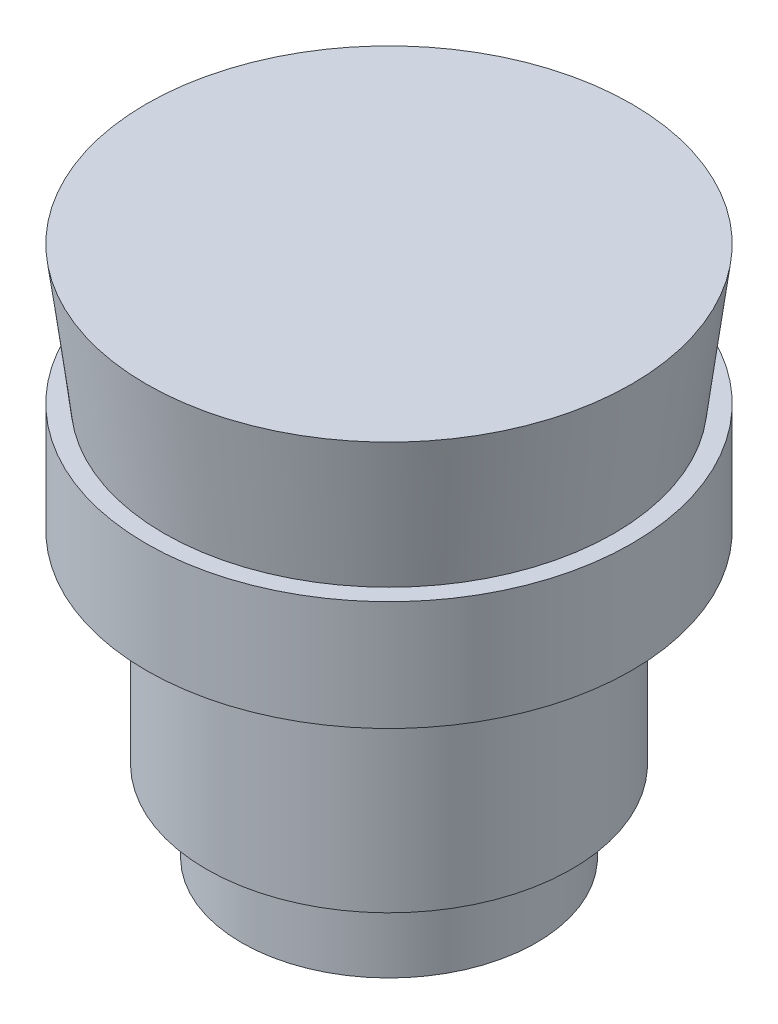
SolidWorks part; units mm, degrees
ref_plane "Front Plane" through (0, 0, 0) normal (0, 0, 1) x (1, 0, 0)
ref_plane "Top Plane" through (0, 0, 0) normal (0, 1, 0) x (1, 0, 0)
ref_plane "Right Plane" through (0, 0, 0) normal (1, 0, 0) x (0, 0, -1)
sketch "Sketch1" plane through (0, 0, 0) normal (1, 0, 0) x (0, 0, -1)
  line L0 (0, 71.6296) -> (0, -39.8706) construction
  line L1 (-49.0321, 0) -> (45.1423, 0) construction
  line L2 (0, 17.78) -> (-17.399, 17.78)
  line L4 (-17.399, 7.874) -> (-17.399, 0)
  line L5 (-17.399, 0) -> (-13.1064, 0)
  line L6 (-13.1064, 0) -> (-13.1064, -14.478)
  line L7 (-13.1064, -14.478) -> (-10.5664, -14.478)
  line L8 (-10.5664, -14.478) -> (-10.5664, -20.32)
  line L9 (-10.5664, -20.32) -> (0, -20.32)
  line L10 (0, 17.78) -> (0, -20.32)
  line L11 (-17.399, 17.78) -> (-16.129, 7.874)
  line L12 (-16.129, 7.874) -> (-17.399, 7.874)
  point P7 (-15.2527, 0)
  point P15 (-14.7026, 7.874)
  dimension "D1" = 17.399
  dimension "D2" = 17.78
  dimension "D3" = 7.874
  dimension "D4" = 14.478
  dimension "D5" = 5.842
  dimension "D6" = 13.1064
  dimension "D7" = 17.399
  dimension "D8" = 2.54
  dimension "D9" = 1.27
revolve "Revolve1" add sketch "Sketch1" angle 360 about L10
cosmetic thread "Cosmetic Thread1" parameters "D1"=2.4999, "D2"=23.8481
